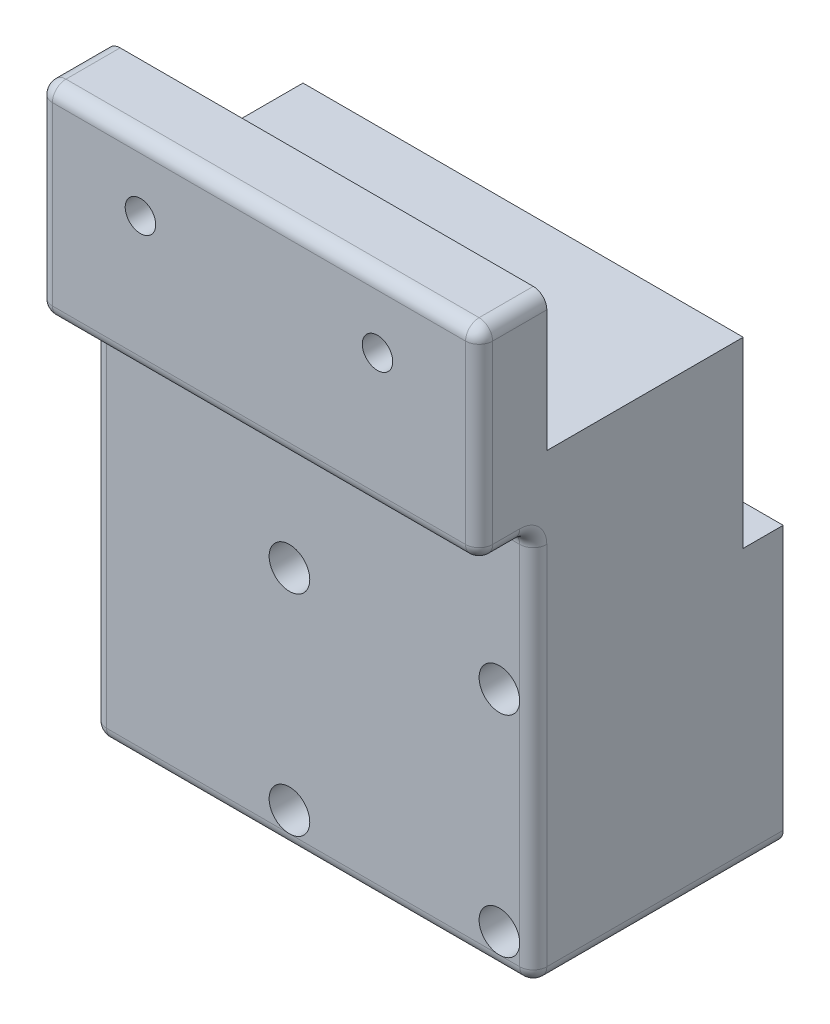
SolidWorks part; units mm, degrees
ref_plane "Front Plane" through (0, 0, 0) normal (0, 0, 1) x (1, 0, 0)
ref_plane "Top Plane" through (0, 0, 0) normal (0, 1, 0) x (1, 0, 0)
ref_plane "Right Plane" through (0, 0, 0) normal (1, 0, 0) x (0, 0, -1)
sketch "Sketch1" plane through (0, 0, 0) normal (0, 0, 1) x (1, 0, 0)
  line L1 (-44.5, 47.5) -> (20.5, 47.5)
  line L2 (-44.5, 47.5) -> (-44.5, -20.5)
  line L3 (-44.5, -20.5) -> (20.5, -20.5)
  line L4 (20.5, 47.5) -> (20.5, -20.5)
  circle A0 centre (0, 0) radius 12
  circle A1 centre (-15.5, 15.5) radius 1.75
  circle A2 centre (15.5, 15.5) radius 1.75
  circle A3 centre (15.5, -15.5) radius 1.75
  circle A4 centre (-15.5, -15.5) radius 1.75
  circle A6 centre (-15.5, 24.5) radius 2.75
  dimension "D1" = 24
  dimension "D2" = 31
  dimension "D3" = 31
  dimension "D4" = 31
  dimension "D5" = 31
  dimension "D6" = 15.5
  dimension "D7" = 15.5
  dimension "D8" = 0
  dimension "D9" = 3.5
  dimension "D10" = 3.5
  dimension "D11" = 3.5
  dimension "D12" = 3.5
  dimension "D13" = 23
  dimension "D14" = 29
  dimension "D16" = 5.5
  dimension "D21" = 47.5
  dimension "D22" = 44.5
  dimension "D19" = 65
  dimension "D20" = 68
extrude "Boss-Extrude1" add sketch "Sketch1" along normal blind 7
sketch "Sketch2" plane through (0, 0, 7) normal (0, 0, 1) x (1, 0, 0)
  line L0 (20.5, 47.5) -> (-44.5, 47.5) construction
  line L1 (-44.5, 47.5) -> (-44.5, -20.5) construction
  circle A0 centre (-15.5, 24.5) radius 2.75
  circle A6 centre (-35.5, 11) radius 2.75
  circle A8 centre (-23.5, -4.2471) radius 2.75
  circle A9 centre (-23.5, -4.2471) radius 7
  circle A10 centre (-15.5, 24.5) radius 7
  circle A11 centre (-35.5, 11) radius 4
  dimension "D1" = 14
  dimension "D2" = 5.5
  dimension "D3" = 5.5
  dimension "D4" = 8
  dimension "D6" = 14
  dimension "D5" = 23
  dimension "D8" = 29
  dimension "D9" = 36.5
  dimension "D10" = 9
  dimension "D11" = 51.7471
  dimension "D7" = 21
extrude "Boss-Extrude2" add sketch "Sketch2" along normal blind 2.65
sketch "Sketch3" plane through (20.5, 0, 0) normal (1, 0, 0) x (0, 0, -1)
  line L1 (-7, 47.5) -> (-29, 47.5)
  line L2 (-7, 47.5) -> (-7, 37.5)
  line L3 (-7, 37.5) -> (-29, 37.5)
  line L4 (-29, 47.5) -> (-29, 37.5)
  line L5 (-29, 37.5) -> (-39, 37.5)
  line L6 (-29, 37.5) -> (-29, 67.5)
  line L7 (-29, 67.5) -> (-39, 67.5)
  line L8 (-39, 37.5) -> (-39, 67.5)
  line M7 (-7, 47.5) -> (-7, -20.5)
  dimension "D1" = 22
  dimension "D2" = 10
  dimension "D3" = 20
  dimension "D4" = 10
extrude "Boss-Extrude3" add sketch "Sketch3" against normal through all contours L1 L4 L3 M7 | L8 L5 L4 L6 L7 region at (20.5, 42.5, 18) region at (20.5, 52.5, 34)
sketch "Sketch4" plane through (0, 0, 39) normal (0, 0, 1) x (1, 0, 0)
  line L0 (-44.5, 37.5) -> (20.5, 37.5) construction
  line L1 (-44.5, 67.5) -> (20.5, 67.5) construction
  line L2 (-44.5, 37.5) -> (-44.5, 67.5) construction
  line L3 (20.5, 37.5) -> (20.5, 67.5) construction
  circle A0 centre (-29.5, 57.5) radius 2.25
  circle A1 centre (5.5, 57.5) radius 2.25
  dimension "D1" = 4.5
  dimension "D2" = 20
  dimension "D3" = 10
  dimension "D4" = 15
  dimension "D5" = 10
  dimension "D6" = 15
  dimension "D7" = 4.5
extrude "Cut-Extrude1" cut sketch "Sketch4" against normal blind 10
sketch "Sketch5" plane through (0, 37.5, 0) normal (0, -1, 0) x (1, 0, 0)
  line L0 (-44.5, 7) -> (-44.5, 39) construction
  line L1 (-44.5, 39) -> (20.5, 39) construction
  line L2 (20.5, 7) -> (20.5, 39) construction
  circle A0 centre (-29.5, 19) radius 2.25
  circle A1 centre (5.5, 19) radius 2.25
  dimension "D1" = 15
  dimension "D2" = 20
  dimension "D3" = 20
  dimension "D4" = 15
  dimension "D5" = 4.5
  dimension "D6" = 4.5
extrude "Cut-Extrude2" cut sketch "Sketch5" against normal blind 10
sketch "Sketch7" plane through (0, 0, 0) normal (0, 0, -1) x (-1, 0, 0)
  line L1 (-20.5, -20.5) -> (20.5, -20.5)
  line L2 (-20.5, -20.5) -> (-20.5, 20.5)
  line L3 (-20.5, 20.5) -> (20.5, 20.5)
  line L4 (20.5, -20.5) -> (20.5, 20.5)
  circle A0 centre (0, 0) radius 12
  circle A1 centre (-15.5, 15.5) radius 1.75
  circle A2 centre (15.5, 15.5) radius 1.75
  circle A3 centre (15.5, -15.5) radius 1.75
  circle A4 centre (-15.5, -15.5) radius 1.75
  dimension "D2" = 5
  dimension "D3" = 5
  dimension "D4" = 5
  dimension "D1" = 5
extrude "Boss-Extrude5" add sketch "Sketch7" along normal blind 5.9
sketch "Sketch8" plane through (0, 0, 9.65) normal (0, 0, 1) x (1, 0, 0)
  circle A0 centre (-35.5, 11) radius 2.75
  circle A1 centre (-35.5, 11) radius 4
  dimension "D1" = 8
extrude "Boss-Extrude6" add sketch "Sketch8" along normal blind 7.95
sketch "Sketch10" plane through (0, 0, 7) normal (0, 0, 1) x (1, 0, 0)
  circle A0 centre (-35.5, 11) radius 2.75
  circle A1 centre (-23.5, -4.2471) radius 2.75
extrude "Cut-Extrude3" cut sketch "Sketch10" against normal blind 9.45
sketch "Sketch11" plane through (0, 0, 7) normal (0, 0, 1) x (1, 0, 0)
  line L1 (-44.5, 37.5) -> (20.5, 37.5)
  line L2 (-44.5, 37.5) -> (-44.5, -20.5)
  line L3 (-44.5, -20.5) -> (20.5, -20.5)
  line L4 (20.5, 37.5) -> (20.5, -20.5)
  circle A0 centre (-23.5, -4.2471) radius 10
  circle A1 centre (-15.5, 24.5) radius 10
  circle A2 centre (-15.5, 24.5) radius 2.75
  circle A3 centre (-23.5, -4.2471) radius 2.75
  circle A4 centre (0, 0) radius 7.25
  circle M1 centre (15.5, -15.5) radius 1.75
  circle M2 centre (-15.5, 15.5) radius 1.75
  circle M3 centre (0, 0) radius 12
  circle M4 centre (15.5, 15.5) radius 1.75
  circle M5 centre (-15.5, -15.5) radius 1.75
  circle M7 centre (-35.5, 11) radius 4
  line M9 (20.5, -20.5) -> (20.5, 37.5)
  line M10 (20.5, 37.5) -> (-44.5, 37.5)
  line M11 (-44.5, 37.5) -> (-44.5, -20.5)
  line M12 (-44.5, -20.5) -> (20.5, -20.5)
  dimension "D1" = 20
  dimension "D2" = 20
  dimension "D3" = 14.5
extrude "Boss-Extrude7" add sketch "Sketch11" along normal blind 10 contours A1 A0 M12 M9 M10 M11 M2 M4 M7 M5 M3 M1 | A4 M3 region at (-12.0095, 9.6819, 7) region at (-11.6606, 0, 7)
sketch "Sketch12" plane through (0, 0, 17) normal (0, 0, 1) x (1, 0, 0)
  line L1 (-11.6164, 26.7733) -> (3.0206, 1.7681)
  line L2 (-44.5, 37.5) -> (-44.5, -20.5) construction
  line L6 (-44.5, -20.5) -> (20.5, -20.5) construction
  line L7 (-44.5, 29) -> (-15.5, 29)
  line L8 (-44.5, 29) -> (-44.5, 32)
  line L9 (-44.5, 32) -> (-15.5, 32)
  line L13 (-9.0274, 28.2888) -> (5.6096, 3.2836)
  line L14 (-21.2843, 2.9181) -> (-1.034, -3.3438)
  line L17 (-22.1706, 0.052) -> (-1.9202, -6.2099)
  line L18 (-31, -4.2471) -> (-31, -20.5)
  line L20 (-31, -20.5) -> (-28, -20.5)
  line L21 (-28, -4.2471) -> (-28, -20.5)
  arc A5 (-21.2843, 2.9181) -> (-31, -4.2471) centre (-23.5, -4.2471) ccw
  arc A6 (-22.1706, 0.052) -> (-28, -4.2471) centre (-23.5, -4.2471) ccw
  arc A7 (-1.034, -3.3438) -> (3.0206, 1.7681) centre (0, 0) ccw
  arc A8 (-11.6164, 26.7733) -> (-15.5, 29) centre (-15.5, 24.5) ccw
  arc A9 (-9.0274, 28.2888) -> (-15.5, 32) centre (-15.5, 24.5) ccw
  arc A10 (-1.9202, -6.2099) -> (5.6096, 3.2836) centre (0, 0) ccw
  dimension "D4" = 3
  dimension "D5" = 3
  dimension "D6" = 3
  dimension "D7" = 3
extrude "Cut-Extrude4" cut sketch "Sketch12" against normal up to surface (7.35 mm away) up to face at (-16.5, -4.2471, 9.65)
sketch "Sketch13" plane through (0, 0, 17) normal (0, 0, 1) x (1, 0, 0)
  line L0 (-44.5, 29) -> (-44.5, -20.5) construction
  line L1 (-15.5, 34.5) -> (-44.5, 34.5)
  line L3 (-15.5, 14.5) -> (-44.5, 14.5)
  line L4 (-44.5, 34.5) -> (-44.5, 14.5)
  line L11 (-23.5, 5.7529) -> (-44.5, 5.7529)
  line L13 (-23.5, -14.2471) -> (-44.5, -14.2471)
  line L14 (-44.5, 5.7529) -> (-44.5, -14.2471)
  arc A0 (-15.5, 14.5) -> (-15.5, 34.5) centre (-15.5, 24.5) ccw
  circle A1 centre (-15.5, 24.5) radius 7
  circle A2 centre (-23.5, -4.2471) radius 7
  arc A4 (-23.5, -14.2471) -> (-23.5, 5.7529) centre (-23.5, -4.2471) ccw
extrude "Cut-Extrude5" cut sketch "Sketch13" against normal up to surface (10 mm away) up to face at (-15.5, 25.875, 7)
sketch "Sketch14" plane through (0, 0, 17) normal (0, 0, 1) x (1, 0, 0)
  circle A0 centre (15.5, 15.5) radius 3
  circle A1 centre (15.5, -15.5) radius 3
  circle A2 centre (-15.5, -15.5) radius 3
  circle A3 centre (-15.5, 15.5) radius 3
  dimension "D1" = 6
extrude "Cut-Extrude6" cut sketch "Sketch14" against normal blind 17
sketch "Sketch15" plane through (0, 0, 17) normal (0, 0, 1) x (1, 0, 0)
  line L0 (-44.5, 37.5) -> (20.5, 37.5)
  line L1 (20.5, 37.5) -> (20.5, -20.5)
  line L8 (-26.9872, 5.7529) -> (-23.5, 5.7529)
  line L9 (-26.1325, 14.5) -> (-18.3284, 14.5)
  line L10 (-15.5, 34.5) -> (-44.5, 34.5)
  line L11 (-44.5, 34.5) -> (-44.5, 37.5)
  line L12 (-14.9652, 0.9641) -> (-7.0998, -1.4681)
  line L13 (-4.9882, -5.2612) -> (-13.6389, -2.5862)
  line L14 (3.9873, 6.055) -> (-5.686, 22.5805)
  line L15 (-7.1051, 19.0663) -> (-0.1869, 7.2476)
  line L18 (-28, -20.5) -> (-28, -14.2471)
  line L19 (-28, -14.2471) -> (-23.5, -14.2471)
  line L21 (-44.5, -20.5) -> (-31, -20.5)
  line L22 (-44.5, -20.5) -> (-44.5, -14.2471)
  line L23 (-44.5, -14.2471) -> (-31, -14.2471)
  line L24 (-31, -20.5) -> (-31, -14.2471)
  line L25 (-28, -20.5) -> (20.5, -20.5)
  arc A0 (-12.5519, 14.9444) -> (-7.1051, 19.0663) centre (-15.5, 24.5) ccw
  arc A1 (-18.3284, 14.5) -> (-12.5519, 14.9444) centre (-15.5, 15.5) ccw
  arc A4 (-4.9882, -5.2612) -> (3.9873, 6.055) centre (0, 0) ccw
  circle A5 centre (15.5, 15.5) radius 3
  circle A6 centre (15.5, -15.5) radius 3
  arc A8 (-0.1869, 7.2476) -> (-7.0998, -1.4681) centre (0, 0) ccw
  arc A12 (-5.686, 22.5805) -> (-15.5, 34.5) centre (-15.5, 24.5) ccw
  circle A15 centre (-15.5, -15.5) radius 3
  arc A18 (-14.9652, 0.9641) -> (-23.5, 5.7529) centre (-23.5, -4.2471) ccw
  arc A19 (-26.9872, 5.7529) -> (-26.1325, 14.5) centre (-35.5, 11) ccw
  arc A20 (-23.5, -14.2471) -> (-13.6389, -2.5862) centre (-23.5, -4.2471) ccw
extrude "Boss-Extrude9" add sketch "Sketch15" along normal blind 3.5
sketch "Sketch16" plane through (0, 0, 20.5) normal (0, 0, 1) x (1, 0, 0)
  line L1 (-44.5, 37.5) -> (20.5, 37.5)
  line L2 (-44.5, 37.5) -> (-44.5, -20.5)
  line L3 (-44.5, -20.5) -> (20.5, -20.5)
  line L4 (20.5, 37.5) -> (20.5, -20.5)
  arc A0 (-44.5, 6.6411) -> (-44.5, 15.3589) centre (-35.5, 11) ccw
  circle A1 centre (-15.5, 15.5) radius 3
  circle A2 centre (15.5, 15.5) radius 3
  circle A3 centre (15.5, -15.5) radius 3
  circle A4 centre (-15.5, -15.5) radius 3
  circle M1 centre (15.5, -15.5) radius 3
  line M2 (-44.5, 37.5) -> (-44.5, 34.5)
  line M3 (-44.5, 34.5) -> (-15.5, 34.5)
  arc M4 (-15.5, 34.5) -> (-5.686, 22.5805) centre (-15.5, 24.5) cw
  line M5 (-5.686, 22.5805) -> (3.9873, 6.055)
  arc M6 (3.9873, 6.055) -> (-4.9882, -5.2612) centre (0, 0) cw
  line M7 (-4.9882, -5.2612) -> (-13.6389, -2.5862)
  arc M8 (-13.6389, -2.5862) -> (-23.5, -14.2471) centre (-23.5, -4.2471) cw
  line M9 (-23.5, -14.2471) -> (-28, -14.2471)
  line M10 (-28, -14.2471) -> (-28, -20.5)
  line M11 (-28, -20.5) -> (20.5, -20.5)
  line M12 (20.5, -20.5) -> (20.5, 37.5)
  line M13 (20.5, 37.5) -> (7.1771, 37.5)
  line M14 (7.1771, 37.5) -> (3.8229, 37.5)
  line M15 (3.8229, 37.5) -> (-27.8229, 37.5)
  line M16 (-27.8229, 37.5) -> (-31.1771, 37.5)
  line M17 (-31.1771, 37.5) -> (-44.5, 37.5)
  circle M18 centre (15.5, 15.5) radius 3
  circle M19 centre (-15.5, -15.5) radius 3
extrude "Boss-Extrude10" add sketch "Sketch16" along normal blind 7.5 contours A0 L2 L3 A1 M10 M9 M8 M7 M6 M5 M4 M3 | M17 M2 M3 M4 M5 M6 M7 M8 M9 M10 M11 M12 M13 M14 M15 M16 M19 M18 M1 region at (2.7798, 8.7673, 20.5) region at (-21.9314, 8.3685, 20.5)
sketch "Sketch17" plane through (0, 0, 28) normal (0, 0, 1) x (1, 0, 0)
  line L1 (-44.5, 37.5) -> (20.5, 37.5)
  line L2 (-44.5, 37.5) -> (-44.5, -20.5)
  line L3 (-44.5, -20.5) -> (20.5, -20.5)
  line L4 (20.5, 37.5) -> (20.5, -20.5)
  circle A0 centre (-15.5, 15.5) radius 3
  circle A1 centre (15.5, 15.5) radius 3
  circle A2 centre (15.5, -15.5) radius 3
  circle A3 centre (-15.5, -15.5) radius 3
extrude "Boss-Extrude11" add sketch "Sketch17" along normal blind 3
sketch "Sketch18" plane through (0, 47.5, 0) normal (0, 1, 0) x (1, 0, 0)
  circle A0 centre (-29.5, -19) radius 2.25
  circle A1 centre (5.5, -19) radius 2.25
extrude "Cut-Extrude7" cut sketch "Sketch18" against normal through all
sketch "Sketch19" plane through (0, -20.5, 0) normal (0, -1, 0) x (1, 0, 0)
  circle A0 centre (-29.5, 19) radius 3.75
  circle A1 centre (5.5, 19) radius 3.75
  dimension "D1" = 7.5
  dimension "D2" = 7.5
extrude "Cut-Extrude8" cut sketch "Sketch19" against normal blind 58
fillet "Fillet2" radius 2 14 edges at (20.5, 37.5, 35) (-44.5, 37.5, 35) (-44.5, 67.5, 34) (20.5, 67.5, 34) (-12, 67.5, 39) (20.5, 52.5, 39) (-44.5, 52.5, 39) (-12, 37.5, 31) (-12, 37.5, 39) (20.5, 8.5, 31) (20.5, -20.5, 12.55) (-12, -20.5, 31) (-44.5, -20.5, 15.5) (-44.5, 8.5, 31)
sketch "Sketch20" plane through (0, 0, 0) normal (0, 0, -1) x (-1, 0, 0)
  line L0 (20.5, 20.5) -> (-20.5, 20.5) construction
  line L1 (13.0463, 28.75) -> (10.5925, 24.5)
  line L2 (10.5925, 24.5) -> (13.0463, 20.25)
  line L3 (13.0463, 20.25) -> (17.9537, 20.25)
  line L4 (17.9537, 20.25) -> (20.4075, 24.5)
  line L5 (20.4075, 24.5) -> (17.9537, 28.75)
  line L6 (17.9537, 28.75) -> (13.0463, 28.75)
  line L7 (39.75, 13.4537) -> (35.5, 15.9075)
  line L8 (35.5, 15.9075) -> (31.25, 13.4537)
  line L9 (31.25, 13.4537) -> (31.25, 8.5463)
  line L10 (31.25, 8.5463) -> (35.5, 6.0925)
  line L11 (35.5, 6.0925) -> (39.75, 8.5463)
  line L12 (39.75, 8.5463) -> (39.75, 13.4537)
  line L13 (23.5, 0.6603) -> (19.25, -1.7934)
  line L14 (19.25, -1.7934) -> (19.25, -6.7009)
  line L15 (19.25, -6.7009) -> (23.5, -9.1546)
  line L16 (23.5, -9.1546) -> (27.75, -6.7009)
  line L17 (27.75, -6.7009) -> (27.75, -1.7934)
  line L18 (27.75, -1.7934) -> (23.5, 0.6603)
  line L19 (20.5, -20.5) -> (20.5, 20.5) construction
  line L20 (20.5, -20.5) -> (20.5, 20.5) construction
  circle A0 centre (15.5, 24.5) radius 4.25 construction
  circle A1 centre (35.5, 11) radius 4.25 construction
  circle A2 centre (23.5, -4.2471) radius 4.25 construction
  point P33 (33.375, 14.6806)
  dimension "D1" = 8.5
extrude "Cut-Extrude9" cut sketch "Sketch20" against normal blind 5.5
sketch "Sketch21" plane through (0, 0, 0) normal (0, 0, -1) x (-1, 0, 0)
  line L1 (17.9537, 28.75) -> (13.0463, 28.75)
  line L2 (13.0463, 28.75) -> (10.5925, 24.5)
  line L3 (10.5925, 24.5) -> (13.0463, 20.25)
  line L4 (13.0463, 20.25) -> (17.9537, 20.25)
  line L5 (17.9537, 20.25) -> (20.4075, 24.5)
  line L6 (20.4075, 24.5) -> (17.9537, 28.75)
  line L7 (27.75, -1.7934) -> (23.5, 0.6603)
  line L8 (23.5, 0.6603) -> (19.25, -1.7934)
  line L9 (19.25, -1.7934) -> (19.25, -6.7009)
  line L10 (19.25, -6.7009) -> (23.5, -9.1546)
  line L11 (23.5, -9.1546) -> (27.75, -6.7009)
  line L12 (27.75, -6.7009) -> (27.75, -1.7934)
  circle A0 centre (15.5, 24.5) radius 4.25 construction
  circle A1 centre (23.5, -4.2471) radius 4.25 construction
extrude "Cut-Extrude10" cut sketch "Sketch21" along normal blind 29.5
